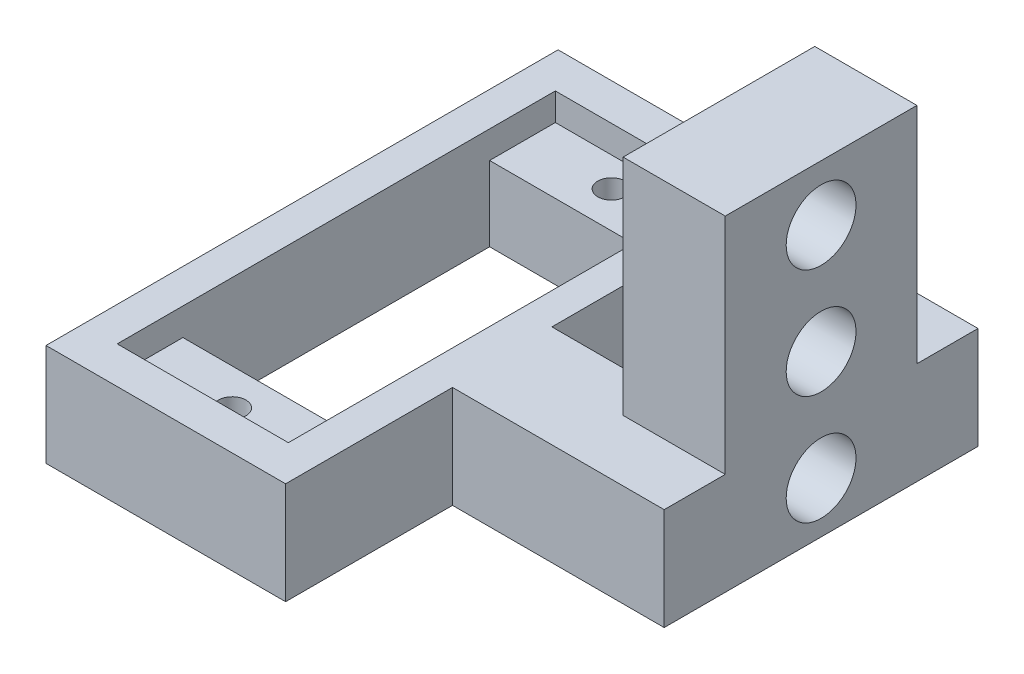
SolidWorks part; units mm, degrees
ref_plane "Front Plane" through (0, 0, 0) normal (0, 0, 1) x (1, 0, 0)
ref_plane "Top Plane" through (0, 0, 0) normal (0, 1, 0) x (1, 0, 0)
ref_plane "Right Plane" through (0, 0, 0) normal (1, 0, 0) x (0, 0, -1)
sketch "Sketch4" plane through (0, 0, 0) normal (0, 1, 0) x (1, 0, 0)
  line L0 (0, 24.3119) -> (0, -27.7936) construction
  line L1 (-27.8941, 0) -> (23.9754, 0) construction
  line L2 (-6.25, -4.95) -> (0, -4.95) construction
  line L3 (8.75, 11.46) -> (24.21, 11.46)
  line L4 (8.55, 4) -> (16.75, 4)
  line L5 (-6.25, 6.25) -> (6.25, 6.25)
  line L6 (6.25, 6.25) -> (6.25, -16.15)
  line L7 (6.25, -16.15) -> (-6.25, -16.15)
  line L8 (-6.25, 6.25) -> (-6.25, -16.15)
  line L9 (8.55, 4) -> (8.55, -4)
  line L10 (8.55, -4) -> (16.75, -4)
  line L11 (16.75, 4) -> (16.75, -4)
  line L12 (8.55, 4) -> (16.75, -4) construction
  line L13 (8.55, -4) -> (16.75, 4) construction
  line L14 (-8.75, 13.75) -> (8.75, 13.75)
  line L15 (-8.75, 13.75) -> (-8.75, -23.65)
  line L16 (-8.75, -23.65) -> (8.75, -23.65)
  line L17 (8.75, 13.75) -> (8.75, 11.46)
  line L18 (-8.75, 13.75) -> (8.75, -23.65) construction
  line L19 (-8.75, -23.65) -> (8.75, 13.75) construction
  line L20 (24.21, 11.46) -> (24.21, -11.46)
  line L21 (8.75, -11.46) -> (24.21, -11.46)
  line L22 (8.75, -11.46) -> (8.75, -23.65)
  circle A0 centre (0, 8.9) radius 1
  circle A1 centre (0, -18.8) radius 1
  point P11 (12.65, 0)
  point P17 (0, -16.15)
  point P18 (0, 6.25)
  point P31 (24.21, 0)
  dimension "D7" = 8
  dimension "D8" = 7.5
  dimension "D4" = 27.7
  dimension "D5" = 2
  dimension "D1" = 22.4
  dimension "D2" = 6.25
  dimension "D3" = 6.25
  dimension "D6" = 8.2
  dimension "D9" = 2.5
  dimension "D10" = 12.65
  dimension "D11" = 7.46
  dimension "D12" = 7.46
extrude "Boss-Extrude2" add sketch "Sketch4" along normal blind 7.46
sketch "Sketch8" plane through (0, 7.46, 0) normal (0, 1, 0) x (1, 0, 0)
  line L0 (16.75, 0) -> (24.21, 0) construction
  line L1 (16.75, -4) -> (16.75, 4) construction
  line L2 (24.21, -11.46) -> (24.21, 11.46) construction
  line L3 (16.75, 7) -> (24.21, 7)
  line L4 (16.75, 7) -> (16.75, -7)
  line L5 (24.21, 7) -> (24.21, -7)
  line L6 (16.75, -7) -> (24.21, -7)
  dimension "D1" = 7
extrude "Boss-Extrude4" add sketch "Sketch8" along normal blind 16.34
sketch "Sketch9" plane through (16.75, 0, 0) normal (-1, 0, 0) x (0, 0, 1)
  line L0 (0, 0) -> (0, 23.8) construction
  line L1 (4, 0) -> (-4, 0) construction
  line L2 (-7, 23.8) -> (7, 23.8) construction
  line L3 (-4, 3.73) -> (4, 3.73) construction
  line L4 (-4, 7.46) -> (-4, 0) construction
  line L5 (4, 7.46) -> (4, 0) construction
  circle A0 centre (0, 3.73) radius 2.55
  circle A1 centre (0, 11.73) radius 2.55
  circle A2 centre (0, 19.73) radius 2.55
  dimension "D1" = 5.1
  dimension "D3" = 8
  dimension "D2" = 3
extrude "Cut-Extrude2" cut sketch "Sketch9" against normal through all
sketch "Sketch12" plane through (0, 7.46, 0) normal (0, 1, 0) x (1, 0, 0)
  line L0 (6.25, -4.95) -> (-6.25, -4.95) construction
  line L1 (6.25, -16.15) -> (6.25, 6.25) construction
  line L2 (-6.25, 6.25) -> (-6.25, -16.15) construction
  line L3 (0, 6.25) -> (0, -16.15) construction
  line L4 (6.25, 6.25) -> (-6.25, 6.25) construction
  line L5 (-6.25, -16.15) -> (6.25, -16.15) construction
  line L7 (6.25, 11.05) -> (-6.25, 11.05)
  line L8 (6.25, 11.05) -> (6.25, -20.95)
  line L9 (6.25, -20.95) -> (-6.25, -20.95)
  line L10 (-6.25, 11.05) -> (-6.25, -20.95)
  line L11 (6.25, 11.05) -> (-6.25, -20.95) construction
  line L12 (6.25, -20.95) -> (-6.25, 11.05) construction
  point P12 (0, -4.95)
  dimension "D1" = 32
  dimension "D2" = 12.5
extrude "Cut-Extrude5" cut sketch "Sketch12" against normal blind 2
sketch "Sketch7" plane through (0, 7.46, 0) normal (0, 1, 0) x (1, 0, 0)
  line L0 (19.9, 3.73) -> (19.9, 11.19)
  line L1 (27.36, 11.19) -> (8.75, 11.19) construction
  line L2 (19.9, 3.73) -> (19.9, -3.73)
  line L3 (19.9, -3.73) -> (19.9, -11.19)
  line L4 (8.75, -11.19) -> (27.36, -11.19) construction
  line L5 (19.9, 11.19) -> (27.36, 11.19)
  line L6 (27.36, 11.19) -> (27.36, -11.19)
  line L7 (27.36, -11.19) -> (19.9, -11.19)
